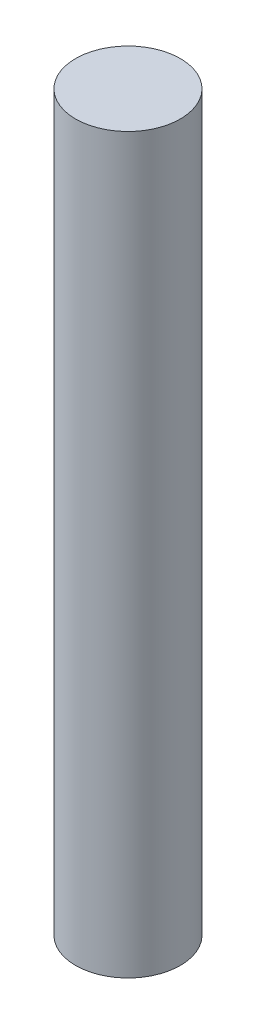
SolidWorks part; units mm, degrees
ref_plane "Front Plane" through (0, 0, 0) normal (0, 0, 1) x (1, 0, 0)
ref_plane "Top Plane" through (0, 0, 0) normal (0, 1, 0) x (1, 0, 0)
ref_plane "Right Plane" through (0, 0, 0) normal (1, 0, 0) x (0, 0, -1)
sketch "Sketch1" plane through (0, 0, 0) normal (0, 1, 0) x (1, 0, 0)
  circle A0 centre (0, 0) radius 2.5
  dimension "D1" = 5
extrude "Boss-Extrude1" add sketch "Sketch1" along normal blind 35 contours A0
